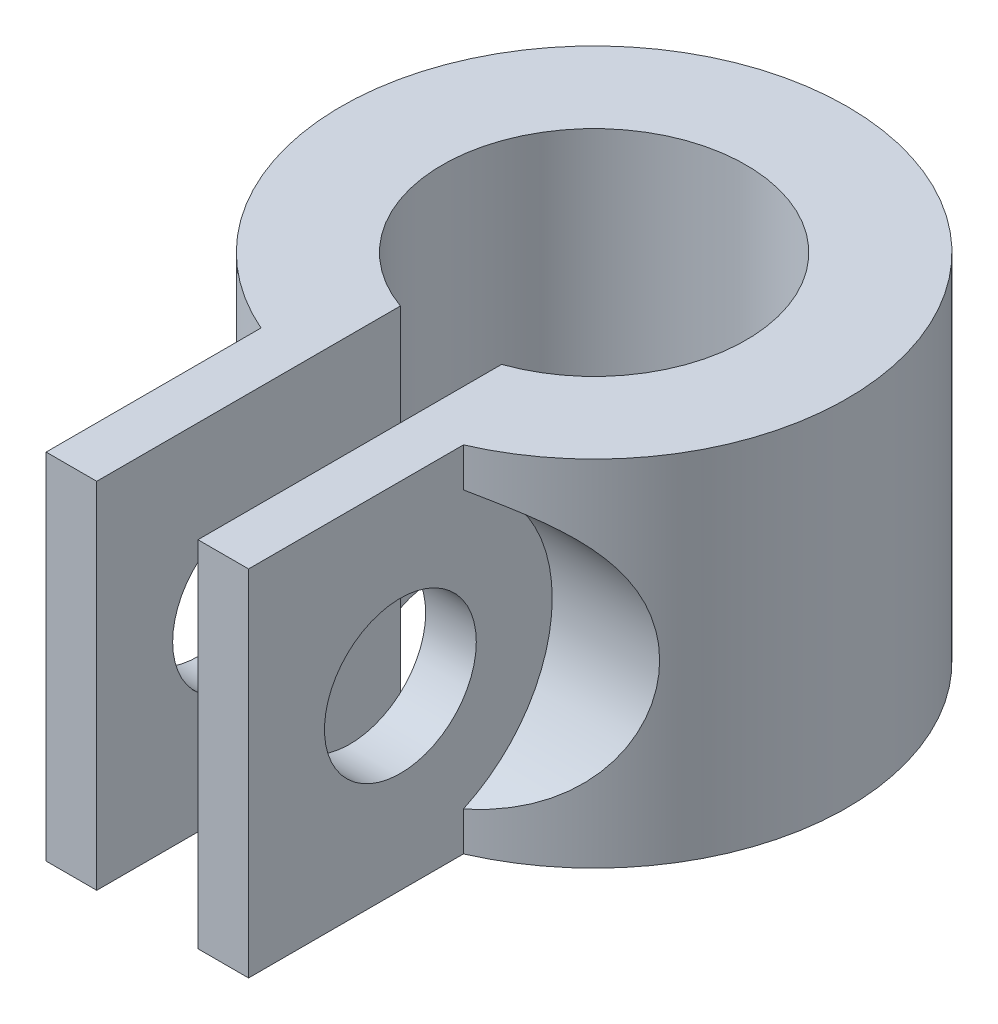
SolidWorks part; units mm, degrees
ref_plane "Front Plane" through (0, 0, 0) normal (0, 0, 1) x (1, 0, 0)
ref_plane "Top Plane" through (0, 0, 0) normal (0, 1, 0) x (1, 0, 0)
ref_plane "Right Plane" through (0, 0, 0) normal (1, 0, 0) x (0, 0, -1)
sketch "Sketch1" plane through (0, 0, 0) normal (0, 1, 0) x (1, 0, 0)
  circle A0 centre (0, 0) radius 3
  circle A1 centre (0, 0) radius 5
  dimension "D1" = 6
  dimension "D2" = 2
extrude "Boss-Extrude1" add sketch "Sketch1" along normal blind 7
sketch "Sketch2" plane through (0, 7, 0) normal (0, 1, 0) x (1, 0, 0)
  line L0 (0, -3.85) -> (0, 3.85) construction
  line L1 (1, -6.8411) -> (-1, -6.8411)
  line L2 (1, -6.8411) -> (1, -1.0103)
  line L3 (1, -1.0103) -> (-1, -1.0103)
  line L4 (-1, -6.8411) -> (-1, -1.0103)
  line L5 (1, -6.8411) -> (-1, -1.0103) construction
  line L6 (1, -1.0103) -> (-1, -6.8411) construction
  point P0 (0, -3.9257)
  point P5 (0, -3.9257)
  dimension "D1" = 2
extrude "Cut-Extrude1" cut sketch "Sketch2" against normal blind 8
sketch "Sketch3" plane through (-1, 0, 0) normal (1, 0, 0) x (0, 0, -1)
  line L1 (-2.8284, 7) -> (-8.8284, 7)
  line L2 (-2.8284, 7) -> (-2.8284, 0)
  line L3 (-2.8284, 0) -> (-8.8284, 0)
  line L4 (-8.8284, 7) -> (-8.8284, 0)
  point P5 (-2.8449, 0)
  point P6 (-2.8449, 0)
  dimension "D1" = 6
extrude "Boss-Extrude2" add sketch "Sketch3" against normal blind 1
mirror "Mirror1" about plane through (0, 0, 0) normal (1, 0, 0) of "Boss-Extrude2"
sketch "Sketch4" plane through (1, 0, 0) normal (-1, 0, 0) x (0, 0, 1)
  line L0 (2.8284, 0) -> (8.8284, 7) construction
  line L1 (8.8284, 0) -> (2.8284, 7) construction
  circle A0 centre (5.8284, 3.5) radius 1.5
  dimension "D1" = 3
extrude "Cut-Extrude2" cut sketch "Sketch4" against normal through all and the other way through all
sketch "Sketch5" plane through (-2, 0, 0) normal (-1, 0, 0) x (0, 0, 1)
  line L0 (8.8284, 0) -> (2.8284, 7) construction
  circle A0 centre (5.8284, 3.5) radius 3
  dimension "D1" = 6
extrude "Cut-Extrude3" cut sketch "Sketch5" along normal through all contours A0
mirror "Mirror2" about plane through (0, 0, 0) normal (1, 0, 0) of "Cut-Extrude3"
